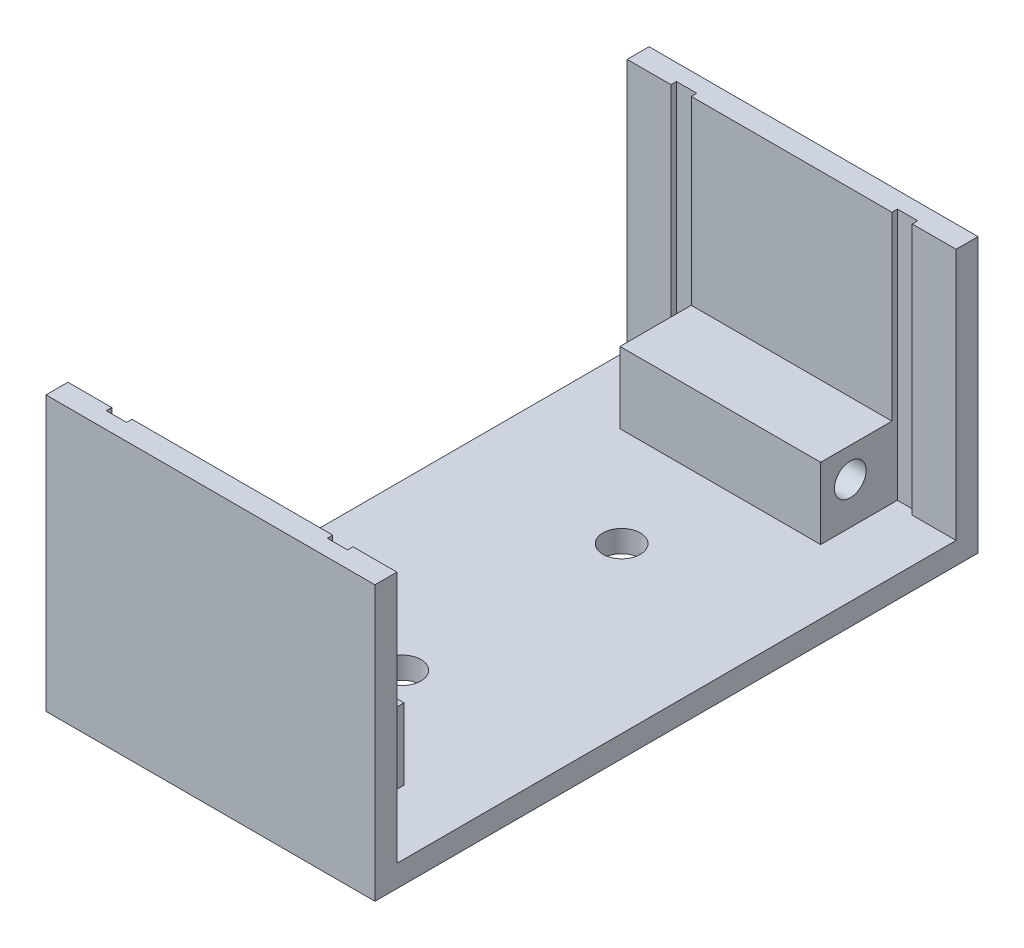
SolidWorks part; units mm, degrees
ref_plane "Front Plane" through (0, 0, 0) normal (0, 0, 1) x (1, 0, 0)
ref_plane "Top Plane" through (0, 0, 0) normal (0, 1, 0) x (1, 0, 0)
ref_plane "Right Plane" through (0, 0, 0) normal (1, 0, 0) x (0, 0, -1)
sketch "Sketch1" plane through (0, 0, 0) normal (0, 1, 0) x (1, 0, 0)
  line L0 (0, 27.5) -> (0, -27.5) construction
  line L1 (-15, 27.5) -> (15, 27.5)
  line L2 (-15, 27.5) -> (-15, -27.5)
  line L3 (-15, -27.5) -> (15, -27.5)
  line L4 (15, 27.5) -> (15, -27.5)
  line L5 (-15, 27.5) -> (15, -27.5) construction
  line L6 (-15, -27.5) -> (15, 27.5) construction
  line L7 (15, 0) -> (-15, 0) construction
  line L8 (-15, 25.5) -> (-11, 25.5)
  line L9 (-11, 25.5) -> (-11, 26)
  line L10 (-11, 26) -> (-9.15, 26)
  line L11 (-9.15, 26) -> (-9.15, 25.5)
  line L12 (-9.15, 25.5) -> (9.15, 25.5)
  line L13 (11, 25.5) -> (11, 26)
  line L14 (9.15, 26) -> (9.15, 25.5)
  line L15 (11, 26) -> (9.15, 26)
  line L16 (-15, 27.5) -> (-15, -27.5)
  line L17 (15, 27.5) -> (15, -27.5)
  line L18 (15, 25.5) -> (11, 25.5)
  line L19 (-15, -25.5) -> (-11, -25.5)
  line L20 (-11, -25.5) -> (-11, -26)
  line L21 (-11, -26) -> (-9.15, -26)
  line L22 (-9.15, -26) -> (-9.15, -25.5)
  line L23 (15, -25.5) -> (11, -25.5)
  line L24 (11, -25.5) -> (11, -26)
  line L25 (11, -26) -> (9.15, -26)
  line L26 (-9.15, -25.5) -> (9.15, -25.5)
  line L27 (9.15, -26) -> (9.15, -25.5)
  point P0 (0, 0)
  point P20 (0, 25.5)
  dimension "D1" = 30
  dimension "D2" = 55
  dimension "D3" = 26
  dimension "D4" = 0.5
  dimension "D5" = 0.5
  dimension "D6" = 1.85
  dimension "D7" = 4
extrude "Boss-Extrude1" add sketch "Sketch1" along normal blind 25 contours L25 L27 L26 L22 L21 L20 L19 L16 L3 L4 L23 L24 | L18 L4 L1 L2 L8 L9 L10 L11 L12 L14 L15 L13 region at (0, 0, -26.5239) region at (0, 0, 26.5239)
extrude "Boss-Extrude2" add sketch "Sketch1<3>" along normal blind 2 contours L27 L25 L24 L23 L17 L18 L13 L15 L14 L12 L11 L10 L9 L8 L2 L19 L20 L21 L22 L26 region at (0, 0, 0)
sketch "Sketch1<3>" plane through (0, 0, 0) normal (0, 1, 0) x (1, 0, 0) same geometry as "Sketch1"
sketch "Sketch2" plane through (0, 2, 0) normal (0, 1, 0) x (1, 0, 0)
  line L0 (0, 25.5) -> (0, -25.5) construction
  line L1 (9.15, -26) -> (9.15, -25.5) construction
  line L3 (-9.15, 25.5) -> (9.15, 25.5) construction
  line L4 (-9.15, -25.5) -> (9.15, -25.5) construction
  line L6 (-9.15, -25.5) -> (9.15, -25.5)
  line L7 (-9.15, -25.5) -> (-9.15, -19)
  line L8 (-9.15, -19) -> (9.15, -19)
  line L9 (9.15, -25.5) -> (9.15, -19)
  dimension "D1" = 6.5
extrude "Boss-Extrude3" add sketch "Sketch2" along normal blind 6.5
sketch "Sketch3" plane through (9.15, 0, 0) normal (1, 0, 0) x (0, 0, -1)
  line L0 (-19, 8.5) -> (-25.5, 8.5) construction
  line L1 (-25.5, 8.5) -> (-25.5, 2) construction
  line L2 (-25.5, 2) -> (-19, 2) construction
  line L3 (-26, 25) -> (-26, 2) construction
  circle A0 centre (-21.7, 5.8) radius 1.45
  dimension "D3" = 2.9
  dimension "D1" = 3.8
  dimension "D2" = 4.3
extrude "Cut-Extrude1" cut sketch "Sketch3" against normal up to next
sketch "Sketch4" plane through (0, 2, 0) normal (0, 1, 0) x (1, 0, 0)
  line L0 (0, -19) -> (0, 25.5) construction
  line L1 (9.15, -19) -> (-9.15, -19) construction
  line L2 (-9.15, 25.5) -> (9.15, 25.5) construction
  line L4 (-2.875, 8.3401) -> (0, 6.6802)
  line L5 (0, 6.6802) -> (2.875, 8.3401)
  line L6 (2.875, 8.3401) -> (2.875, 11.6599)
  line L7 (2.875, 11.6599) -> (0, 13.3198)
  line L8 (0, 13.3198) -> (-2.875, 11.6599)
  line L9 (-2.875, 11.6599) -> (-2.875, 8.3401)
  line L10 (0, -13.3198) -> (2.875, -11.6599)
  line L11 (2.875, -11.6599) -> (2.875, -8.3401)
  line L12 (2.875, -8.3401) -> (0, -6.6802)
  line L13 (0, -6.6802) -> (-2.875, -8.3401)
  line L14 (-2.875, -8.3401) -> (-2.875, -11.6599)
  line L15 (-2.875, -11.6599) -> (0, -13.3198)
  line L17 (15, 0) -> (-15, 0) construction
  line L18 (15, 25.5) -> (15, -25.5) construction
  line L19 (-15, 25.5) -> (-15, -25.5) construction
  circle A0 centre (0, 10) radius 2.875 construction
  circle A1 centre (0, -10) radius 2.875 construction
  circle A4 centre (0, 10) radius 1.7
  circle A5 centre (0, -10) radius 1.7
  dimension "D3" = 5.75
  dimension "D4" = 5.75
  dimension "D5" = 3.4
  dimension "D1" = 10
  dimension "D2" = 10
extrude "Cut-Extrude3" cut sketch "Sketch4" against normal up to next contours A4 | A5 region at (0, 2, -10) region at (0, 2, 10)
mirror "Mirror1" about plane through (0, 0, 0) normal (0, 0, 1) of "Cut-Extrude1", "Boss-Extrude3"
